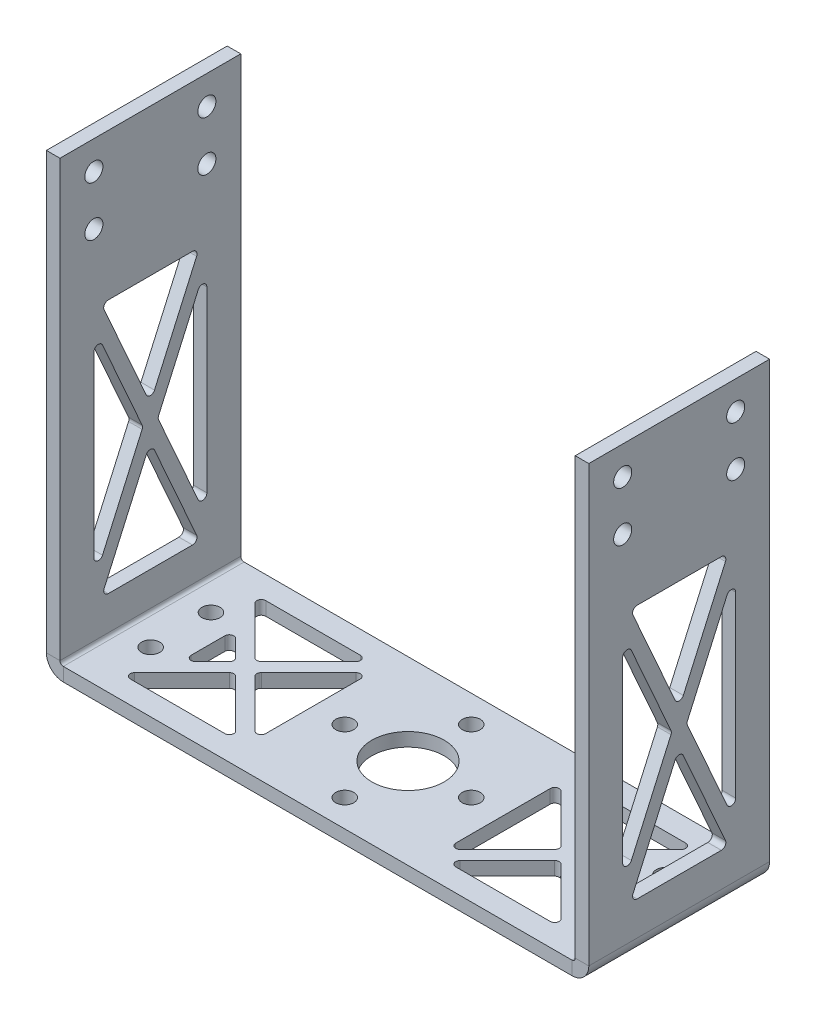
SolidWorks part; units mm, degrees
note: The reader was unsure of these and kept them because the rebuilt part matched: flange length of "Edge-Flange1", "Edge-Flange2".
material "Alloy Steel (SS)"
ref_plane "Front Plane" through (0, 0, 0) normal (0, 0, 1) x (1, 0, 0)
ref_plane "Top Plane" through (0, 0, 0) normal (0, 1, 0) x (1, 0, 0)
ref_plane "Right Plane" through (0, 0, 0) normal (1, 0, 0) x (0, 0, -1)
sketch "Sketch3" plane through (0, 0, 0) normal (0, 1, 0) x (1, 0, 0)
  line L6 (-57, 20) -> (57, 20)
  line L18 (-57, 20) -> (-57, -20)
  line L19 (-57, -20) -> (57, -20)
  line L20 (57, 20) -> (57, -20)
  line L21 (-57, 20) -> (57, -20) construction
  line L22 (-57, -20) -> (57, 20) construction
  point P0 (0, 0)
  dimension "D1" = 40
  dimension "D2" = 114
base flange "Base-Flange1" sketch "Sketch3" thickness 3 reverse thickness direction no parameters "D1"=0.7366
edge flange "Edge-Flange1" sketch "Sketch7" flange angle 90 flange length 100 flange position material outside bend radius 0.7366 thickness 3 relief rectangular parameters "D6"=10
sketch "Sketch7" plane through (-57, 0, 0) normal (-1, 0, 0) x (0, 0, 1)
  line L0 (-20, 0) -> (20, 0) construction
  line L1 (-20, 0) -> (20, 0)
  line L2 (-20, 0) -> (-20, 97)
  line L3 (-20, 97) -> (20, 97)
  line L4 (20, 97) -> (20, 0)
bend "EdgeBend1" bend radius 0.7366 bend angle 90 parameters "D5"=1
edge flange "Edge-Flange2" sketch "Sketch10" flange angle 90 flange length 100 flange position material outside bend radius 0.7366 thickness 3 relief rectangular parameters "D6"=10
sketch "Sketch10" plane through (57, 0, 0) normal (1, 0, 0) x (0, 0, -1)
  line L0 (-20, 0) -> (20, 0) construction
  line L1 (-20, 0) -> (20, 0)
  line L2 (-20, 0) -> (-20, 97)
  line L3 (-20, 97) -> (20, 97)
  line L4 (20, 97) -> (20, 0)
bend "EdgeBend2" bend radius 0.7366 bend angle 90 parameters "D5"=2
sketch "Sketch11" plane through (0, -3, 0) normal (0, -1, 0) x (-1, 0, 0)
  line L0 (-56.2634, 20) -> (56.2634, -20) construction
  line L1 (56.2634, 20) -> (-56.2634, -20) construction
  line L2 (0, 20) -> (0, 8) construction
  line L3 (-56.2634, 20) -> (56.2634, 20) construction
  line L4 (-50.2634, -20) -> (-50.2634, -6.6667) construction
  line L5 (56.2634, -20) -> (-56.2634, -20) construction
  line L6 (-50.2634, -6.6667) -> (-50.2634, 6.6667) construction
  line L7 (-50.2634, 6.6667) -> (-50.2634, 20) construction
  line L8 (50.2634, -20) -> (50.2634, -6.6667) construction
  line L9 (50.2634, -6.6667) -> (50.2634, 6.6667) construction
  line L10 (50.2634, 6.6667) -> (50.2634, 20) construction
  line L11 (50.2634, 0) -> (56.2634, 0) construction
  line L12 (56.2634, -20) -> (56.2634, 20) construction
  line L13 (-50.2634, 0) -> (-56.2634, 0) construction
  line L14 (-56.2634, 20) -> (-56.2634, -20) construction
  circle A0 centre (0, 0) radius 8
  circle A1 centre (0, 14) radius 2
  circle A2 centre (14, 0) radius 2
  circle A3 centre (0, -14) radius 2
  circle A4 centre (-14, 0) radius 2
  circle A5 centre (50.2634, 6.6667) radius 2
  circle A6 centre (-50.2634, 6.6667) radius 2
  circle A7 centre (50.2634, -6.6667) radius 2
  circle A8 centre (-50.2634, -6.6667) radius 2
  point P20 (0, 14)
  point P29 (0, 0)
  dimension "D1" = 16
  dimension "D2" = 4
  dimension "D4" = 6
  dimension "D3" = 4
extrude "Cut-Extrude1" cut sketch "Sketch11" against normal blind 10 normal cut yes
sketch "Sketch12" plane through (60, 0, 0) normal (1, 0, 0) x (0, 0, -1)
  circle A0 centre (12.5, 79.6742) radius 2
  circle A1 centre (12.5, 90.6742) radius 2
  circle A2 centre (-12.5, 79.6742) radius 2
  circle A3 centre (-12.5, 90.6742) radius 2
  dimension "D1" = 4
  dimension "D2" = 4
  dimension "D3" = 4
  dimension "D4" = 4
extrude "Cut-Extrude2" cut sketch "Sketch12" against normal up to surface (120 mm away) normal cut yes up to face at (-60, 48.8683, 0)
sketch "Sketch14" plane through (60, 0, 0) normal (1, 0, 0) x (0, 0, -1)
  line L0 (-12.5, 64.5) -> (12.5, 8.2366) construction
  line L5 (-12.5, 60.8059) -> (-1.6414, 36.3683)
  line L6 (-12.5, 8.2366) -> (12.5, 64.5) construction
  line L7 (-12.5, 72) -> (-12.5, 64.5) construction
  line L32 (-17, 72) -> (-8, 72) construction
  line L33 (-12.5, 64.5) -> (-20, 64.5) construction
  line L34 (-20, 97) -> (-20, 0.7366) construction
  line L35 (12.5, 72) -> (12.5, 64.5) construction
  line L36 (8, 72) -> (17, 72) construction
  line L37 (12.5, 64.5) -> (20, 64.5) construction
  line L38 (20, 0.7366) -> (20, 97) construction
  line L39 (12.5, 0.7366) -> (12.5, 8.2366) construction
  line L40 (20, 0.7366) -> (-20, 0.7366) construction
  line L41 (12.5, 8.2366) -> (20, 8.2366) construction
  line L42 (-12.5, 0.7366) -> (-12.5, 8.2366) construction
  line L43 (-12.5, 8.2366) -> (-20, 8.2366) construction
  line L44 (-1.6414, 36.3683) -> (-12.5, 11.9307)
  line L45 (-12.5, 11.9307) -> (-12.5, 60.8059)
  line L46 (-10.8586, 64.5) -> (0, 40.0624)
  line L47 (0, 40.0624) -> (10.8586, 64.5)
  line L48 (10.8586, 64.5) -> (-10.8586, 64.5)
  line L49 (12.5, 60.8059) -> (1.6414, 36.3683)
  line L50 (1.6414, 36.3683) -> (12.5, 11.9307)
  line L51 (12.5, 11.9307) -> (12.5, 60.8059)
  line L52 (10.8586, 8.2366) -> (0, 32.6742)
  line L53 (0, 32.6742) -> (-10.8586, 8.2366)
  line L54 (-10.8586, 8.2366) -> (10.8586, 8.2366)
  line L55 (-8.6204, 52.0747) -> (-7.2496, 52.6838) construction
  line L56 (-4.4648, 50.1105) -> (-5.8356, 49.5014) construction
  line L57 (8.9336, 52.7797) -> (7.5629, 53.3888) construction
  line L58 (4.7494, 50.7511) -> (6.1202, 50.1421) construction
  line L59 (7.3086, 16.2261) -> (8.6793, 16.8352) construction
  line L60 (6.7233, 24.9312) -> (5.3526, 24.3222) construction
  line L61 (-6.4395, 25.5699) -> (-5.0688, 24.9609) construction
  line L62 (-7.2868, 16.275) -> (-8.6576, 16.8841) construction
  dimension "D1" = 1.5
extrude "Cut-Extrude3" cut sketch "Sketch14" against normal through all both and the other way through all normal cut yes
sketch "Sketch15" plane through (0, -3, 0) normal (0, -1, 0) x (1, 0, 0)
  line L0 (44.2634, -8.2634) -> (21, 15) construction
  line L1 (21, 15) -> (21, -15) construction
  line L2 (21, -15) -> (44.2634, 8.2634) construction
  line L3 (44.2634, 8.2634) -> (44.2634, -8.2634) construction
  line L4 (44.2634, -8.2634) -> (44.2634, -20) construction
  line L5 (56.2634, -20) -> (-56.2634, -20) construction
  line L6 (44.2634, -8.2634) -> (56.2634, -8.2634) construction
  line L7 (56.2634, -20) -> (56.2634, 20) construction
  line L8 (44.2634, 8.2634) -> (56.2634, 8.2634) construction
  line L9 (44.2634, 8.2634) -> (44.2634, 20) construction
  line L10 (-56.2634, 20) -> (56.2634, 20) construction
  line L11 (21, 15) -> (21, 20) construction
  line L12 (21, -15) -> (21, -20) construction
  line L13 (16, 20) -> (16, -20) construction
  line L14 (21, 15) -> (16, 15) construction
  line L15 (21, -15) -> (16, -15) construction
  line L16 (21, 12.8787) -> (33.8787, 0)
  line L17 (33.8787, 0) -> (21, -12.8787)
  line L18 (21, -12.8787) -> (21, 12.8787)
  line L19 (23.1213, 15) -> (36, 2.1213)
  line L20 (36, 2.1213) -> (48.8787, 15)
  line L21 (48.8787, 15) -> (23.1213, 15)
  line L22 (44.2634, 6.1421) -> (38.1213, 0)
  line L23 (38.1213, 0) -> (44.2634, -6.1421)
  line L24 (44.2634, -6.1421) -> (44.2634, 6.1421)
  line L25 (48.8787, -15) -> (36, -2.1213)
  line L26 (36, -2.1213) -> (23.1213, -15)
  line L27 (23.1213, -15) -> (48.8787, -15)
  line L28 (23.975, 9.9037) -> (25.0357, 10.9643) construction
  line L29 (29.6377, 8.4836) -> (28.577, 7.423) construction
  line L30 (40.35, 6.4713) -> (41.4106, 5.4106) construction
  line L31 (45.3558, 7.2345) -> (44.2951, 8.2951) construction
  line L32 (42.9486, -9.0699) -> (44.0093, -8.0093) construction
  line L33 (42.4106, -4.2892) -> (41.3499, -5.3499) construction
  line L34 (27.8604, -6.0183) -> (28.921, -7.079) construction
  line L35 (26.0292, -9.9708) -> (27.0899, -11.0315) construction
  line L36 (0, 14) -> (0, -14) construction
  line L37 (-26.0292, -9.9708) -> (-27.0899, -11.0315) construction
  line L38 (-27.8604, -6.0183) -> (-28.921, -7.079) construction
  line L39 (-42.4106, -4.2892) -> (-41.3499, -5.3499) construction
  line L40 (-42.9486, -9.0699) -> (-44.0093, -8.0093) construction
  line L41 (-45.3558, 7.2345) -> (-44.2951, 8.2951) construction
  line L42 (-40.35, 6.4713) -> (-41.4106, 5.4106) construction
  line L43 (-29.6377, 8.4836) -> (-28.577, 7.423) construction
  line L44 (-23.975, 9.9037) -> (-25.0357, 10.9643) construction
  line L45 (-21, -15) -> (-16, -15) construction
  line L46 (-21, 15) -> (-16, 15) construction
  line L47 (-16, 20) -> (-16, -20) construction
  line L48 (-21, -15) -> (-21, -20) construction
  line L49 (-21, 15) -> (-21, 20) construction
  line L50 (-44.2634, 8.2634) -> (-44.2634, 20) construction
  line L51 (-44.2634, 8.2634) -> (-56.2634, 8.2634) construction
  line L52 (-44.2634, -8.2634) -> (-56.2634, -8.2634) construction
  line L53 (-44.2634, -8.2634) -> (-44.2634, -20) construction
  line L54 (-44.2634, 8.2634) -> (-44.2634, -8.2634) construction
  line L55 (-21, -15) -> (-44.2634, 8.2634) construction
  line L56 (-21, 15) -> (-21, -15) construction
  line L57 (-44.2634, -8.2634) -> (-21, 15) construction
  line L58 (-23.1213, -15) -> (-48.8787, -15)
  line L59 (-36, -2.1213) -> (-23.1213, -15)
  line L60 (-48.8787, -15) -> (-36, -2.1213)
  line L61 (-44.2634, -6.1421) -> (-44.2634, 6.1421)
  line L62 (-38.1213, 0) -> (-44.2634, -6.1421)
  line L63 (-44.2634, 6.1421) -> (-38.1213, 0)
  line L64 (-48.8787, 15) -> (-23.1213, 15)
  line L65 (-36, 2.1213) -> (-48.8787, 15)
  line L66 (-23.1213, 15) -> (-36, 2.1213)
  line L67 (-21, -12.8787) -> (-21, 12.8787)
  line L68 (-33.8787, 0) -> (-21, -12.8787)
  line L69 (-21, 12.8787) -> (-33.8787, 0)
  circle A0 centre (14, 0) radius 2 construction
  point P94 (46.7445, -15)
  point P97 (0, 0)
  point P98 (49.694, -15)
  point P99 (45.348, -9.0699)
  point P100 (45.2444, -7.079)
  dimension "D1" = 5
  dimension "D2" = 1.5
  dimension "D3" = 12
extrude "Cut-Extrude4" cut sketch "Sketch15" against normal blind 10 normal cut yes
fillet "Fillet1" radius 1 48 edges at (-58.5, 40.0624, 0) (-58.5, 32.6742, 0) (-58.5, 64.5, 10.8586) (-58.5, 8.2366, 10.8586) (-58.5, 36.3683, -1.6414) (-58.5, 8.2366, -10.8586) (-58.5, 64.5, -10.8586) (-58.5, 36.3683, 1.6414) (58.5, 36.3683, -1.6414) (58.5, 36.3683, 1.6414) (58.5, 40.0624, 0) (58.5, 64.5, 10.8586) (58.5, 64.5, -10.8586) (58.5, 60.8059, 12.5) (58.5, 60.8059, -12.5) (58.5, 32.6742, 0) (58.5, 11.9307, -12.5) (58.5, 11.9307, 12.5) (58.5, 8.2366, 10.8586) (58.5, 8.2366, -10.8586) (21, -1.5, -12.8787) (-44.2634, -1.5, -6.1421) (36, -1.5, 2.1213) (-23.1213, -1.5, -15) (48.8787, -1.5, -15) (44.2634, -1.5, -6.1421) (-36, -1.5, 2.1213) (-21, -1.5, -12.8787) (44.2634, -1.5, 6.1421) (-21, -1.5, 12.8787) (33.8787, -1.5, 0) (48.8787, -1.5, 15) (-23.1213, -1.5, 15) (-38.1213, -1.5, 0) (21, -1.5, 12.8787) (36, -1.5, -2.1213) (-44.2634, -1.5, 6.1421) (-36, -1.5, -2.1213) (23.1213, -1.5, 15) (-48.8787, -1.5, 15) (23.1213, -1.5, -15) (38.1213, -1.5, 0) (-33.8787, -1.5, 0) (-48.8787, -1.5, -15)
sketch "Bend-Lines1" [suppressed] plane through (0, 0, 0) normal (0, 1, 0) x (1, 0, 0)
sketch "Bounding-Box1" [suppressed] plane through (0, 0, 0) normal (0, 1, 0) x (1, 0, 0)
sheet metal parameters "Sheet-Metal1" thickness 3 parameters "D1"=0.7366
flat pattern "Flat-Pattern1" [suppressed]
sketch "Bend-Lines2" plane through (0, 0, 0) normal (0, 1, 0) x (1, 0, 0)
sketch3d "Bounding-Box2" [suppressed]
  line L0 (57, -20, 0) -> (-57, -20, 0) construction
  line L1 (57, 20, 0) -> (-57, 20, 0) construction
  line L2 (57, -20, 0) -> (57, 20, 0) construction
  line L3 (-57, -20, 0) -> (-57, 20, 0) construction
sheet metal parameters "Sheet-Metal2" thickness 3 parameters "D1"=0.7366
flat pattern "Flat-Pattern1"
sketch "Bend-Lines2" plane through (0, 0, 0) normal (0, 1, 0) x (1, 0, 0)
  line L0 (-58.02, 20) -> (-58.02, -20) construction
  line L1 (-58.02, 20) -> (-58.02, -20) construction
sketch3d "Bounding-Box2" [suppressed]
  line L0 (57, -20, 0) -> (-90.7766, -20, 0) construction
  line L1 (57, 20, 0) -> (-90.7766, 20, 0) construction
  line L2 (57, -20, 0) -> (57, 20, 0) construction
  line L3 (-90.7766, -20, 0) -> (-90.7766, 20, 0) construction
bend of the flat pattern "Flatten-<EdgeBend1>1"
sheet metal parameters "Sheet-Metal3" thickness 3 parameters "D1"=0.7366
flat pattern "Flat-Pattern1"
sketch "Bend-Lines2" plane through (0, 0, 0) normal (0, 1, 0) x (1, 0, 0)
  line L0 (-58.02, 20) -> (-58.02, -20) construction
  line L1 (-58.02, 20) -> (-58.02, -20) construction
  line L2 (58.02, -20) -> (58.02, 20) construction
  line L3 (58.02, -20) -> (58.02, 20) construction
sketch3d "Bounding-Box2" [suppressed]
  line L0 (156.04, -20, 0) -> (-156.04, -20, 0) construction
  line L1 (156.04, 20, 0) -> (-156.04, 20, 0) construction
  line L2 (156.04, -20, 0) -> (156.04, 20, 0) construction
  line L3 (-156.04, -20, 0) -> (-156.04, 20, 0) construction
bend of the flat pattern "Flatten-<EdgeBend1>1"
bend of the flat pattern "Flatten-<EdgeBend2>1"
sheet metal parameters "Sheet-Metal4" thickness 3 parameters "D1"=0.7366
flat pattern "Flat-Pattern1"
sketch "Bend-Lines2" plane through (0, 0, 0) normal (0, 1, 0) x (1, 0, 0)
  line L0 (-58.02, 20) -> (-58.02, -20) construction
  line L1 (-58.02, 20) -> (-58.02, -20) construction
  line L2 (58.02, -20) -> (58.02, 20) construction
  line L3 (58.02, -20) -> (58.02, 20) construction
sketch3d "Bounding-Box2" [suppressed]
  line L0 (156.04, -20, 0) -> (-156.04, -20, 0) construction
  line L1 (156.04, 20, 0) -> (-156.04, 20, 0) construction
  line L2 (156.04, -20, 0) -> (156.04, 20, 0) construction
  line L3 (-156.04, -20, 0) -> (-156.04, 20, 0) construction
bend of the flat pattern "Flatten-<EdgeBend1>1"
bend of the flat pattern "Flatten-<EdgeBend2>1"
sheet metal parameters "Sheet-Metal5" thickness 3 parameters "D1"=0.7366
flat pattern "Flat-Pattern1"
sketch "Bend-Lines2" plane through (0, 0, 0) normal (0, 1, 0) x (1, 0, 0)
  line L0 (-58.02, 20) -> (-58.02, -20) construction
  line L1 (-58.02, 20) -> (-58.02, -20) construction
  line L2 (58.02, -20) -> (58.02, 20) construction
  line L3 (58.02, -20) -> (58.02, 20) construction
sketch3d "Bounding-Box2" [suppressed]
  line L0 (156.04, -20, 0) -> (-156.04, -20, 0) construction
  line L1 (156.04, 20, 0) -> (-156.04, 20, 0) construction
  line L2 (156.04, -20, 0) -> (156.04, 20, 0) construction
  line L3 (-156.04, -20, 0) -> (-156.04, 20, 0) construction
bend of the flat pattern "Flatten-<EdgeBend1>1"
bend of the flat pattern "Flatten-<EdgeBend2>1"
sheet metal parameters "Sheet-Metal6" thickness 3 parameters "D1"=0.7366
flat pattern "Flat-Pattern1"
sketch "Bend-Lines2" plane through (0, 0, 0) normal (0, 1, 0) x (1, 0, 0)
  line L0 (-58.02, 20) -> (-58.02, -20) construction
  line L1 (-58.02, 20) -> (-58.02, -20) construction
  line L2 (58.02, -20) -> (58.02, 20) construction
  line L3 (58.02, -20) -> (58.02, 20) construction
sketch3d "Bounding-Box2" [suppressed]
  line L0 (156.04, -20, 0) -> (-156.04, -20, 0) construction
  line L1 (156.04, 20, 0) -> (-156.04, 20, 0) construction
  line L2 (156.04, -20, 0) -> (156.04, 20, 0) construction
  line L3 (-156.04, -20, 0) -> (-156.04, 20, 0) construction
bend of the flat pattern "Flatten-<EdgeBend1>1"
bend of the flat pattern "Flatten-<EdgeBend2>1"
sheet metal parameters "Sheet-Metal7" thickness 3 parameters "D1"=0.7366
flat pattern "Flat-Pattern1"
sketch "Bend-Lines2" plane through (0, 0, 0) normal (0, 1, 0) x (1, 0, 0)
  line L0 (-58.02, 20) -> (-58.02, -20) construction
  line L1 (-58.02, 20) -> (-58.02, -20) construction
  line L2 (58.02, -20) -> (58.02, 20) construction
  line L3 (58.02, -20) -> (58.02, 20) construction
sketch3d "Bounding-Box2" [suppressed]
  line L0 (156.04, -20, 0) -> (-156.04, -20, 0) construction
  line L1 (156.04, 20, 0) -> (-156.04, 20, 0) construction
  line L2 (156.04, -20, 0) -> (156.04, 20, 0) construction
  line L3 (-156.04, -20, 0) -> (-156.04, 20, 0) construction
bend of the flat pattern "Flatten-<EdgeBend1>1"
bend of the flat pattern "Flatten-<EdgeBend2>1"
